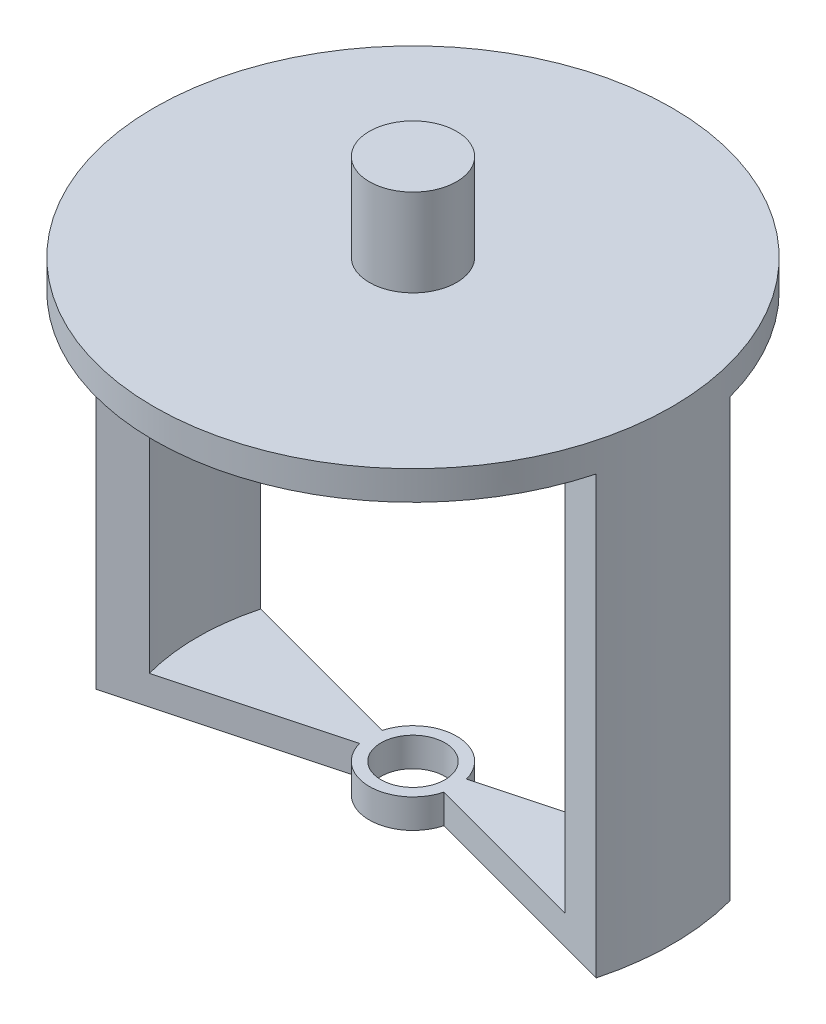
SolidWorks part; units mm, degrees
ref_plane "Alzado" through (0, 0, 0) normal (0, 0, 1) x (1, 0, 0)
ref_plane "Planta" through (0, 0, 0) normal (0, 1, 0) x (1, 0, 0)
ref_plane "Vista lateral" through (0, 0, 0) normal (1, 0, 0) x (0, 0, -1)
sketch "Croquis1" plane through (0, 0, 0) normal (0, 1, 0) x (1, 0, 0)
  circle A0 centre (0, 0) radius 44.5
  dimension "D1" = 89
extrude "Saliente-Extruir1" add sketch "Croquis1" along normal blind 40 and the other way blind 40
sketch "Croquis2" plane through (0, 0, 0) normal (0, 1, 0) x (1, 0, 0)
  line L0 (0, 0) -> (52.2565, 0) construction
  line L1 (0, 0) -> (42.9837, 11.5174) construction
  line L2 (0, 0) -> (42.9837, -11.5174) construction
  line L3 (0, 44.5) -> (0, -44.5) construction
  line L4 (35.7393, 9.5763) -> (42.9837, 11.5174)
  line L5 (35.7393, -9.5763) -> (42.9837, -11.5174)
  line L6 (-35.7393, -9.5763) -> (-42.9837, -11.5174)
  line L7 (-35.7393, 9.5763) -> (-42.9837, 11.5174)
  circle A0 centre (0, 0) radius 44.5 construction
  circle A1 centre (0, 0) radius 44.5 construction
  arc A2 (-42.9837, -11.5174) -> (-42.9837, 11.5174) centre (0, 0) cw
  arc A3 (-35.7393, -9.5763) -> (-35.7393, 9.5763) centre (0, 0) cw
  arc A4 (35.7393, -9.5763) -> (35.7393, 9.5763) centre (0, 0) ccw
  arc A5 (42.9837, -11.5174) -> (42.9837, 11.5174) centre (0, 0) ccw
  point P1 (0, 0)
  point P12 (0, 0)
  dimension "D1" = 15
  dimension "D2" = 7.5
extrude "Cortar-Extruir1" cut sketch "Croquis2" against normal blind 35 and the other way blind 35 flip side to cut
sketch "Croquis3" plane through (0, -35, 0) normal (0, 1, 0) x (1, 0, 0)
  line L0 (-42.9837, -11.5174) -> (-35.7393, -9.5763) construction
  line L1 (42.9837, 11.5174) -> (7.2444, 1.9411)
  line L2 (42.9837, -11.5174) -> (7.2444, -1.9411)
  line L3 (-42.9837, -11.5174) -> (-7.2444, -1.9411)
  line L4 (-42.9837, 11.5174) -> (-7.2444, 1.9411)
  circle A0 centre (0, 0) radius 44.5 construction
  circle A1 centre (0, 0) radius 5.5
  arc A5 (-42.9837, -11.5174) -> (42.9837, -11.5174) centre (0, 0) ccw
  arc A6 (7.2444, 1.9411) -> (-7.2444, 1.9411) centre (0, 0) ccw
  arc A7 (42.9837, 11.5174) -> (-42.9837, 11.5174) centre (0, 0) ccw
  arc A8 (-7.2444, -1.9411) -> (7.2444, -1.9411) centre (0, 0) ccw
  arc M4 (-42.9837, -11.5174) -> (42.9837, -11.5174) centre (0, 0) ccw
  line M5 (42.9837, -11.5174) -> (35.7393, -9.5763)
  line M7 (35.7393, 9.5763) -> (42.9837, 11.5174)
  arc M8 (42.9837, 11.5174) -> (-42.9837, 11.5174) centre (0, 0) ccw
  line M26 (-42.9837, 11.5174) -> (-35.7393, 9.5763)
  line M28 (-35.7393, -9.5763) -> (-42.9837, -11.5174)
  dimension "D1" = 7.5
  dimension "D2" = 11
extrude "Cortar-Extruir2" cut sketch "Croquis3" against normal up to next contours A8 L3 M28 M4 | A8 L2 M5 | A6 L1 M8 M7 | A7 L4 A6 M26 | A1 | A1 region at (0, -35, -22.4236) region at (0, -35, 22.4236) region at (0, -35, 0)
sketch "Croquis4" plane through (0, 40, 0) normal (0, 1, 0) x (1, 0, 0)
  circle A0 centre (0, 0) radius 7.5
  dimension "D1" = 15
extrude "Saliente-Extruir2" add sketch "Croquis4" along normal blind 15
